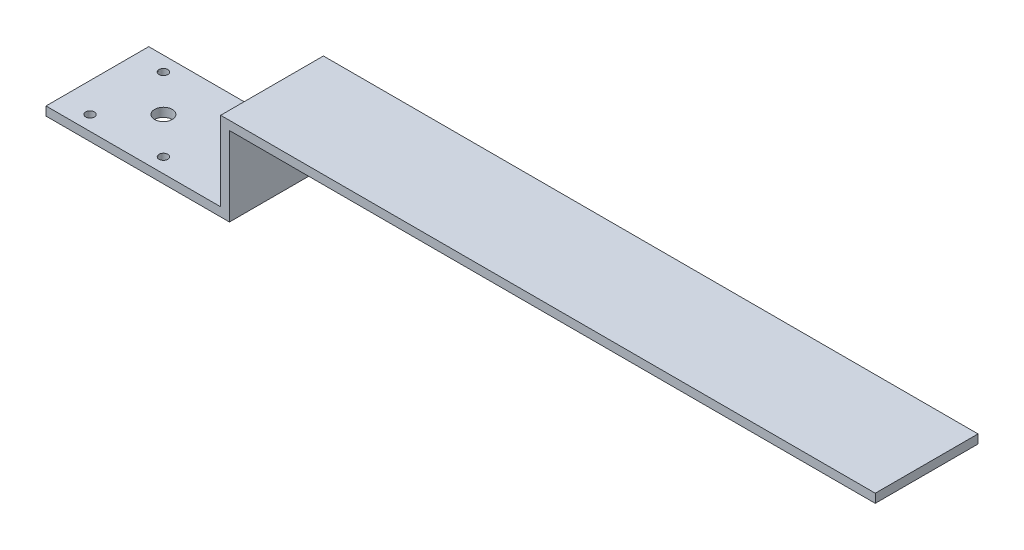
SolidWorks part; units mm, degrees
ref_plane "Front Plane" through (0, 0, 0) normal (0, 0, 1) x (1, 0, 0)
ref_plane "Top Plane" through (0, 0, 0) normal (0, 1, 0) x (1, 0, 0)
ref_plane "Right Plane" through (0, 0, 0) normal (1, 0, 0) x (0, 0, -1)
sketch "Sketch1" plane through (0, 0, 0) normal (0, 1, 0) x (1, 0, 0)
  line L0 (-31.25, 0) -> (0, 0) construction
  line L1 (-31.25, 17.5) -> (31.25, 17.5)
  line L2 (-31.25, 17.5) -> (-31.25, -17.5)
  line L3 (-31.25, -17.5) -> (31.25, -17.5)
  line L4 (31.25, 17.5) -> (31.25, -17.5)
  line L5 (-31.25, 17.5) -> (31.25, -17.5) construction
  line L6 (-31.25, -17.5) -> (31.25, 17.5) construction
  line L7 (3.75, 12.5) -> (-21.25, -12.5) construction
  circle A0 centre (-21.25, 12.5) radius 1.5
  circle A1 centre (-21.25, -12.5) radius 1.5
  circle A2 centre (3.75, 12.5) radius 1.5
  circle A3 centre (3.75, -12.5) radius 1.5
  circle A4 centre (-8.75, 0) radius 3
  point P0 (0, 0)
  dimension "D3" = 25
  dimension "D4" = 12.5
  dimension "D5" = 3
  dimension "D6" = 3
  dimension "D8" = 10
  dimension "D9" = 3
  dimension "D10" = 3
  dimension "D12" = 25
  dimension "D13" = 25
  dimension "D14" = 12.5
  dimension "D15" = 6
  dimension "D16" = 40
  dimension "D2" = 35
  dimension "D7" = 10
  dimension "D11" = 25
extrude "Boss-Extrude1" add sketch "Sketch1" along normal blind 3
sketch "Sketch3" plane through (0, 3, 0) normal (0, 1, 0) x (1, 0, 0)
  line L0 (-31.25, -17.5) -> (31.25, -17.5) construction
  line L1 (31.25, 17.5) -> (28.25, 17.5)
  line L2 (31.25, 17.5) -> (31.25, -17.5)
  line L3 (31.25, -17.5) -> (28.25, -17.5)
  line L4 (28.25, 17.5) -> (28.25, -17.5)
  dimension "D1" = 3
extrude "Boss-Extrude3" add sketch "Sketch3" along normal blind 27
sketch "Sketch4" plane through (31.25, 0, 0) normal (1, 0, 0) x (0, 0, -1)
  line L0 (17.5, 30) -> (17.5, 0) construction
  line L1 (-17.5, 30) -> (17.5, 30)
  line L2 (-17.5, 30) -> (-17.5, 27)
  line L3 (-17.5, 27) -> (17.5, 27)
  line L4 (17.5, 30) -> (17.5, 27)
  dimension "D1" = 3
extrude "Boss-Extrude4" add sketch "Sketch4" along normal blind 220
sketch "Sketch5" plane through (31.25, 0, 0) normal (1, 0, 0) x (0, 0, -1)
  line L1 (17.5, 27) -> (17.5, 0) construction
  line L2 (-17.5, 27) -> (17.5, 27) construction
  circle A0 centre (12.5, 24) radius 1.5
  dimension "D1" = 3
  dimension "D2" = 5
  dimension "D3" = 3
extrude "Cut-Extrude1" cut sketch "Sketch5" against normal blind 10
